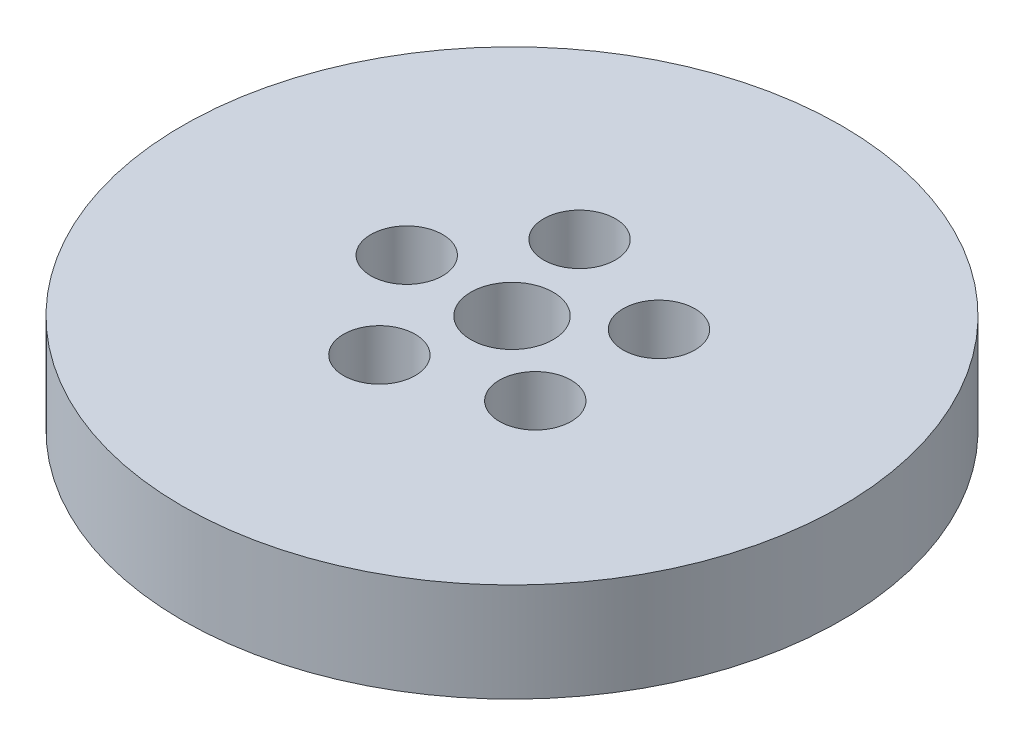
SolidWorks part; units mm, degrees
ref_plane "Front Plane" through (0, 0, 0) normal (0, 0, 1) x (1, 0, 0)
ref_plane "Top Plane" through (0, 0, 0) normal (0, 1, 0) x (1, 0, 0)
ref_plane "Right Plane" through (0, 0, 0) normal (1, 0, 0) x (0, 0, -1)
sketch "Sketch1" plane through (0, 0, 0) normal (0, 1, 0) x (1, 0, 0)
  circle A0 centre (0, 0) radius 40
  dimension "FLANGE_OD" = 80
extrude "Boss-Extrude1" add sketch "Sketch1" along normal blind 12
sketch "Sketch2" plane through (0, 0, 0) normal (0, 1, 0) x (1, 0, 0)
  circle A0 centre (0, 0) radius 5
  dimension "BORE_D" = 10
extrude "Cut-Extrude1" cut sketch "Sketch2" along normal through all
sketch "Sketch3" plane through (0, 12, 0) normal (0, 1, 0) x (1, 0, 0)
  circle A0 centre (0, 0) radius 12.7739 construction
  circle A1 centre (-12.7739, 0) radius 4.353
  dimension "BOLT_D" = 8.7059
  dimension "BOLT_PCD" = 25.5478
extrude "Cut-Extrude2" cut sketch "Sketch3" against normal blind 9.7097
pattern_circular "CirPattern1" count 5 over 360 about axis through (0, 0, 0) along (0, 1, 0) of "Cut-Extrude2"
